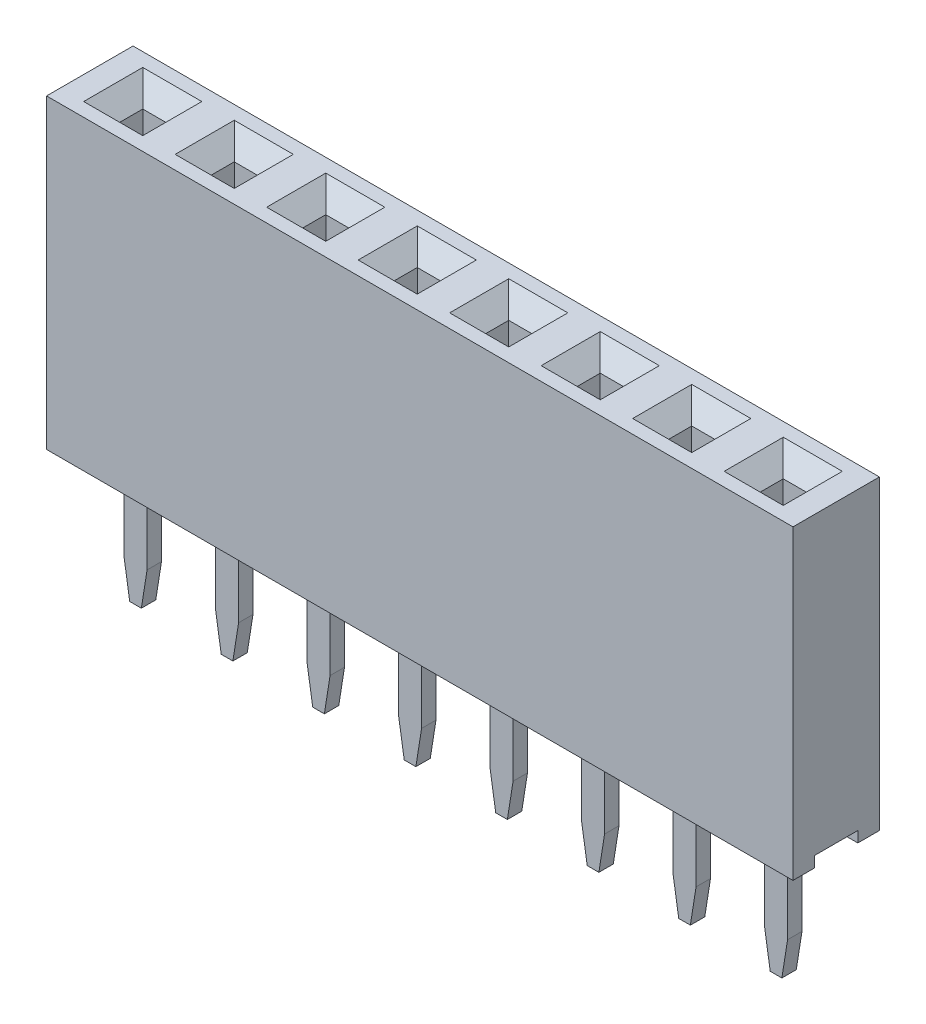
SolidWorks part; units mm, degrees
ref_plane "Front Plane" through (0, 0, 0) normal (0, 0, 1) x (1, 0, 0)
ref_plane "Top Plane" through (0, 0, 0) normal (0, 1, 0) x (1, 0, 0)
ref_plane "Right Plane" through (0, 0, 0) normal (1, 0, 0) x (0, 0, -1)
sketch "Sketch1" plane through (0, 0, 0) normal (0, 1, 0) x (1, 0, 0)
  line L1 (0, 0) -> (20.72, 0)
  line L2 (0, 0) -> (0, 2.4)
  line L3 (0, 2.4) -> (20.72, 2.4)
  line L4 (20.72, 0) -> (20.72, 2.4)
  dimension "D1" = 2.4
  dimension "D2" = 20.72
extrude "Boss-Extrude1" add sketch "Sketch1" along normal blind 8.5
sketch "Sketch3" plane through (0, 0, 0) normal (0, -1, 0) x (1, 0, 0)
  line L0 (0, -1.2) -> (20.72, -1.2) construction
  line L1 (0, -2.4) -> (0, 0) construction
  line L2 (20.72, 0) -> (20.72, -2.4) construction
  line L4 (0, -1.8) -> (20.72, -1.8)
  line L5 (0, -1.8) -> (0, -0.6)
  line L6 (0, -0.6) -> (20.72, -0.6)
  line L7 (20.72, -1.8) -> (20.72, -0.6)
  line L8 (0, -1.8) -> (20.72, -0.6) construction
  line L9 (0, -0.6) -> (20.72, -1.8) construction
  point P6 (10.36, -1.2)
  dimension "D1" = 1.2
extrude "Cut-Extrude1" cut sketch "Sketch3" against normal blind 0.3
sketch "Sketch4" plane through (0, 8.5, 0) normal (0, 1, 0) x (1, 0, 0)
  line L0 (0, 1.2) -> (20.72, 1.2) construction
  line L1 (0, 2.4) -> (0, 0) construction
  line L2 (20.72, 0) -> (20.72, 2.4) construction
  line L3 (3.69, 0.88) -> (3.69, 1.52)
  line L4 (1.15, 0.88) -> (1.79, 0.88)
  line L5 (1.15, 0.88) -> (1.15, 1.52)
  line L6 (1.15, 1.52) -> (1.79, 1.52)
  line L7 (1.79, 0.88) -> (1.79, 1.52)
  line L8 (1.15, 0.88) -> (1.79, 1.52) construction
  line L9 (1.15, 1.52) -> (1.79, 0.88) construction
  line L10 (3.69, 0.88) -> (4.33, 0.88)
  line L11 (4.33, 0.88) -> (4.33, 1.52)
  line L12 (3.69, 1.52) -> (4.33, 1.52)
  line L13 (6.23, 0.88) -> (6.23, 1.52)
  line L14 (6.23, 0.88) -> (6.87, 0.88)
  line L15 (6.87, 0.88) -> (6.87, 1.52)
  line L16 (6.23, 1.52) -> (6.87, 1.52)
  line L17 (8.77, 0.88) -> (8.77, 1.52)
  line L18 (8.77, 0.88) -> (9.41, 0.88)
  line L19 (9.41, 0.88) -> (9.41, 1.52)
  line L20 (8.77, 1.52) -> (9.41, 1.52)
  line L21 (11.31, 0.88) -> (11.31, 1.52)
  line L22 (11.31, 0.88) -> (11.95, 0.88)
  line L23 (11.95, 0.88) -> (11.95, 1.52)
  line L24 (11.31, 1.52) -> (11.95, 1.52)
  line L25 (13.85, 0.88) -> (13.85, 1.52)
  line L26 (13.85, 0.88) -> (14.49, 0.88)
  line L27 (14.49, 0.88) -> (14.49, 1.52)
  line L28 (13.85, 1.52) -> (14.49, 1.52)
  line L29 (16.39, 0.88) -> (16.39, 1.52)
  line L30 (16.39, 0.88) -> (17.03, 0.88)
  line L31 (17.03, 0.88) -> (17.03, 1.52)
  line L32 (16.39, 1.52) -> (17.03, 1.52)
  line L33 (18.93, 0.88) -> (18.93, 1.52)
  line L34 (18.93, 0.88) -> (19.57, 0.88)
  line L35 (19.57, 0.88) -> (19.57, 1.52)
  line L36 (18.93, 1.52) -> (19.57, 1.52)
  line L37 (1.15, 0.88) -> (3.69, 0.88) construction
  point P6 (1.47, 1.2)
  dimension "D1" = 0.64
  dimension "D2" = 0.64
  dimension "D3" = 1.47
  dimension "D5" = 2.54
  dimension "D4" = 8
extrude "Cut-Extrude2" cut sketch "Sketch4" against normal blind 6
chamfer "Chamfer2" distance 0.5 angle 45 32 edges at (1.47, 8.5, -1.52) (1.15, 8.5, -1.2) (1.47, 8.5, -0.88) (1.79, 8.5, -1.2) (4.01, 8.5, -1.52) (3.69, 8.5, -1.2) (4.01, 8.5, -0.88) (4.33, 8.5, -1.2) (6.55, 8.5, -1.52) (6.23, 8.5, -1.2) (6.55, 8.5, -0.88) (6.87, 8.5, -1.2) (8.77, 8.5, -1.2) (9.09, 8.5, -0.88) (9.41, 8.5, -1.2) (9.09, 8.5, -1.52) (11.63, 8.5, -1.52) (11.31, 8.5, -1.2) (11.63, 8.5, -0.88) (11.95, 8.5, -1.2) (14.49, 8.5, -1.2) (14.17, 8.5, -1.52) (13.85, 8.5, -1.2) (14.17, 8.5, -0.88) (16.71, 8.5, -1.52) (16.39, 8.5, -1.2) (16.71, 8.5, -0.88) (17.03, 8.5, -1.2) (19.57, 8.5, -1.2) (19.25, 8.5, -1.52) (18.93, 8.5, -1.2) (19.25, 8.5, -0.88)
sketch "Sketch5" plane through (0, 0.3, 0) normal (0, -1, 0) x (1, 0, 0)
  line L0 (0, -1.2) -> (20.72, -1.2) construction
  line L1 (0, -0.6) -> (0, -1.8) construction
  line L2 (20.72, -1.8) -> (20.72, -0.6) construction
  line L3 (3.69, -1.4) -> (3.69, -1)
  line L4 (1.15, -1.4) -> (1.79, -1.4)
  line L5 (1.15, -1.4) -> (1.15, -1)
  line L6 (1.15, -1) -> (1.79, -1)
  line L7 (1.79, -1.4) -> (1.79, -1)
  line L8 (1.15, -1.4) -> (1.79, -1) construction
  line L9 (1.15, -1) -> (1.79, -1.4) construction
  line L10 (3.69, -1.4) -> (4.33, -1.4)
  line L11 (4.33, -1.4) -> (4.33, -1)
  line L12 (3.69, -1) -> (4.33, -1)
  line L13 (6.23, -1.4) -> (6.23, -1)
  line L14 (6.23, -1.4) -> (6.87, -1.4)
  line L15 (6.87, -1.4) -> (6.87, -1)
  line L16 (6.23, -1) -> (6.87, -1)
  line L17 (8.77, -1.4) -> (8.77, -1)
  line L18 (8.77, -1.4) -> (9.41, -1.4)
  line L19 (9.41, -1.4) -> (9.41, -1)
  line L20 (8.77, -1) -> (9.41, -1)
  line L21 (11.31, -1.4) -> (11.31, -1)
  line L22 (11.31, -1.4) -> (11.95, -1.4)
  line L23 (11.95, -1.4) -> (11.95, -1)
  line L24 (11.31, -1) -> (11.95, -1)
  line L25 (13.85, -1.4) -> (13.85, -1)
  line L26 (13.85, -1.4) -> (14.49, -1.4)
  line L27 (14.49, -1.4) -> (14.49, -1)
  line L28 (13.85, -1) -> (14.49, -1)
  line L29 (16.39, -1.4) -> (16.39, -1)
  line L30 (16.39, -1.4) -> (17.03, -1.4)
  line L31 (17.03, -1.4) -> (17.03, -1)
  line L32 (16.39, -1) -> (17.03, -1)
  line L33 (18.93, -1.4) -> (18.93, -1)
  line L34 (18.93, -1.4) -> (19.57, -1.4)
  line L35 (19.57, -1.4) -> (19.57, -1)
  line L36 (18.93, -1) -> (19.57, -1)
  line L37 (1.15, -1.4) -> (3.69, -1.4) construction
  point P6 (1.47, -1.2)
  dimension "D1" = 0.4
  dimension "D2" = 0.64
  dimension "D3" = 1.47
  dimension "D5" = 2.54
  dimension "D4" = 8
extrude "Boss-Extrude2" add sketch "Sketch5" along normal blind 3.8
chamfer "Chamfer3" distance 1 angle 9 16 edges at (19.57, -3.5, -1.2) (18.93, -3.5, -1.2) (17.03, -3.5, -1.2) (16.39, -3.5, -1.2) (14.49, -3.5, -1.2) (13.85, -3.5, -1.2) (11.95, -3.5, -1.2) (11.31, -3.5, -1.2) (9.41, -3.5, -1.2) (8.77, -3.5, -1.2) (6.87, -3.5, -1.2) (6.23, -3.5, -1.2) (4.33, -3.5, -1.2) (3.69, -3.5, -1.2) (1.79, -3.5, -1.2) (1.15, -3.5, -1.2) first distance on face at (19.57, -1.6, -1.2) first distance on face at (18.93, -1.6, -1.2) first distance on face at (17.03, -1.6, -1.2) first distance on face at (16.39, -1.6, -1.2) first distance on face at (14.49, -1.6, -1.2) first distance on face at (13.85, -1.6, -1.2) first distance on face at (11.95, -1.6, -1.2) first distance on face at (11.31, -1.6, -1.2) first distance on face at (9.41, -1.6, -1.2) first distance on face at (8.77, -1.6, -1.2) first distance on face at (6.87, -1.6, -1.2) first distance on face at (6.23, -1.6, -1.2) first distance on face at (4.33, -1.6, -1.2) first distance on face at (3.69, -1.6, -1.2) first distance on face at (1.79, -1.6, -1.2) first distance on face at (1.15, -1.6, -1.2)
